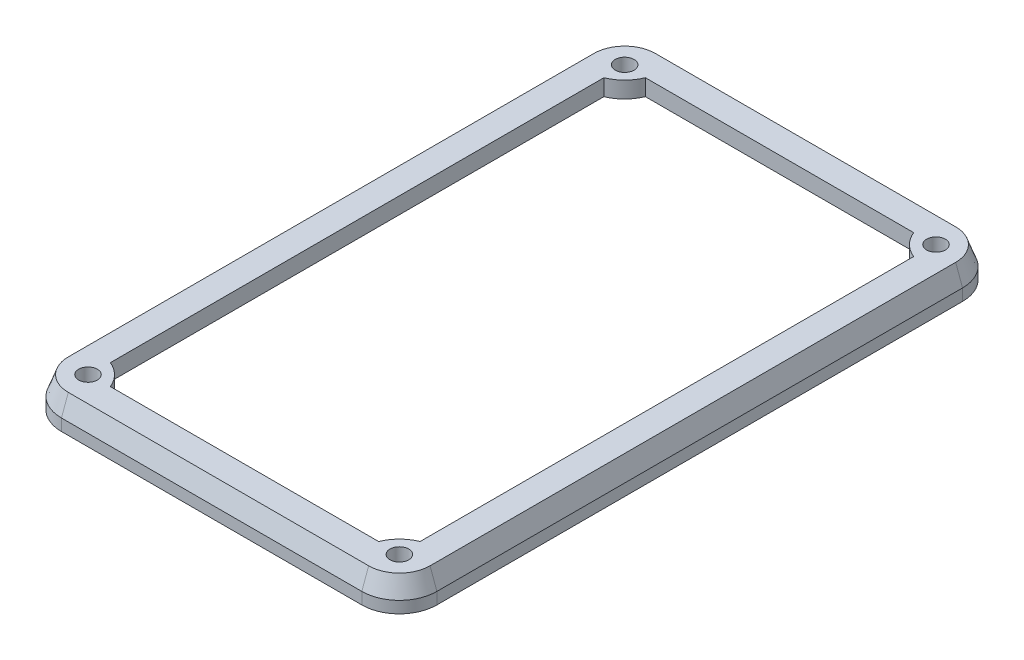
SolidWorks part; units mm, degrees
ref_plane "Front Plane" through (0, 0, 0) normal (0, 0, 1) x (1, 0, 0)
ref_plane "Top Plane" through (0, 0, 0) normal (0, 1, 0) x (1, 0, 0)
ref_plane "Right Plane" through (0, 0, 0) normal (1, 0, 0) x (0, 0, -1)
sketch "Sketch1" plane through (0, 0, 0) normal (0, 1, 0) x (1, 0, 0)
  line L1 (20, -32) -> (-20, -32)
  line L2 (20, -32) -> (20, 32)
  line L3 (20, 32) -> (-20, 32)
  line L4 (-20, -32) -> (-20, 32)
  line L5 (20, -32) -> (-20, 32) construction
  line L6 (20, 32) -> (-20, -32) construction
  line L7 (18, -30) -> (-18, -30)
  line L8 (18, -30) -> (18, 30)
  line L9 (18, 30) -> (-18, 30)
  line L10 (-18, -30) -> (-18, 30)
  line L11 (18, -30) -> (-18, 30) construction
  line L12 (18, 30) -> (-18, -30) construction
  point P0 (0, 0)
  point P6 (0, 0)
  dimension "D1" = 40
  dimension "D2" = 64
  dimension "D3" = 2
  dimension "D4" = 2
extrude "Boss-Extrude1" add sketch "Sketch1" along normal blind 3.25
sketch "Sketch3" plane through (0, 3.25, 0) normal (0, 1, 0) x (1, 0, 0)
  line L0 (-14.2919, -28.5) -> (14.2919, -28.5)
  line L1 (-18, 26) -> (-18, 30)
  line L2 (-18, 30) -> (-14, 30)
  line L4 (0, 27.3879) -> (0, -1.4953) construction
  line L5 (-16.5, 26.2919) -> (-16.5, -26.2919)
  line L6 (-17, 0) -> (17, 0) construction
  line L7 (-14.2919, 28.5) -> (14.2919, 28.5)
  line L9 (-18, 30) -> (-15.1716, 27.1716) construction
  line L11 (-18, 30) -> (-18, 26)
  line L12 (-14, 30) -> (-18, 30)
  line L13 (18, 30) -> (15.1716, 27.1716) construction
  line L14 (14, 30) -> (18, 30)
  line L15 (18, 30) -> (18, 26)
  line L16 (18, 30) -> (14, 30)
  line L17 (18, 26) -> (18, 30)
  line L18 (18, -30) -> (15.1716, -27.1716) construction
  line L19 (-18, -30) -> (-15.1716, -27.1716) construction
  line L20 (18, -26) -> (18, -30)
  line L21 (18, -30) -> (14, -30)
  line L22 (18, -30) -> (18, -26)
  line L23 (14, -30) -> (18, -30)
  line L24 (-14, -30) -> (-18, -30)
  line L25 (-18, -30) -> (-18, -26)
  line L26 (-18, -30) -> (-14, -30)
  line L27 (-18, -26) -> (-18, -30)
  line L28 (-18, 30) -> (-18, -30) construction
  line L29 (18, 30) -> (-18, 30) construction
  line L30 (16.5, 26.2919) -> (16.5, -26.2919)
  circle A1 centre (-16.5858, 28.5858) radius 1
  arc A4 (-18, 26) -> (-14, 30) centre (-18, 30) ccw
  arc A5 (18, 26) -> (14, 30) centre (18, 30) cw
  circle A6 centre (16.5858, 28.5858) radius 1
  circle A7 centre (16.5858, -28.5858) radius 1
  arc A8 (18, -26) -> (14, -30) centre (18, -30) ccw
  arc A9 (-18, -26) -> (-14, -30) centre (-18, -30) cw
  circle A10 centre (-16.5858, -28.5858) radius 1
  point P3 (-18, 0)
  point P11 (0, 30)
  point P23 (0, 0)
  line M105 (18, -30) -> (-18, -30)
  line M106 (-18, -30) -> (-18, 30)
  line M107 (-18, 30) -> (18, 30)
  line M108 (18, 30) -> (18, -30)
  dimension "D2" = 2
  dimension "D1" = 4
  dimension "D3" = 1.5
  dimension "D4" = 1.5
extrude "Boss-Extrude2" add sketch "Sketch3" against normal offset from surface (1.75 mm away) 1.5 contours A4 A1 M106 M107 | A6 A5 M108 M107 | A8 L21 A7 M108 | A9 L24 A10 M106 | A9 L5 A4 M106 | L0 A9 A8 M105 | A8 A5 L30 M108 | L7 A5 A4 M107 region at (-14.1292, 3.25, 29.2467) region at (0, 3.25, 29.2474) region at (15.2116, 3.25, 27.2116) region at (-17.2486, 3.25, 0) region at (17.2486, 3.25, 0) region at (-17.2467, 3.25, -26.1292) region at (15.2116, 3.25, -27.2116) region at (0, 3.25, -29.2474) up to face at (0, 0, 0)
fillet "Fillet1" radius 4 4 edges at (20, 1.625, -32) (-20, 1.625, -32) (20, 1.625, 32) (-20, 1.625, 32)
chamfer "Chamfer1" distance 2 angle 20 8 edges at (20, 3.25, 0) (18.8284, 3.25, 30.8284) (0, 3.25, -32) (0, 3.25, 32) (-18.8284, 3.25, -30.8284) (-18.8284, 3.25, 30.8284) (-20, 3.25, 0) (18.8284, 3.25, -30.8284) first distance on face at (20, 1.625, 0) first distance on face at (18.4142, 1.625, 30.4142) first distance on face at (0, 1.625, -32) first distance on face at (0, 1.625, 32) first distance on face at (-18.4142, 1.625, -30.4142) first distance on face at (-18.4142, 1.625, 30.4142) first distance on face at (-20, 1.625, 0) first distance on face at (18.4142, 1.625, -30.4142)
